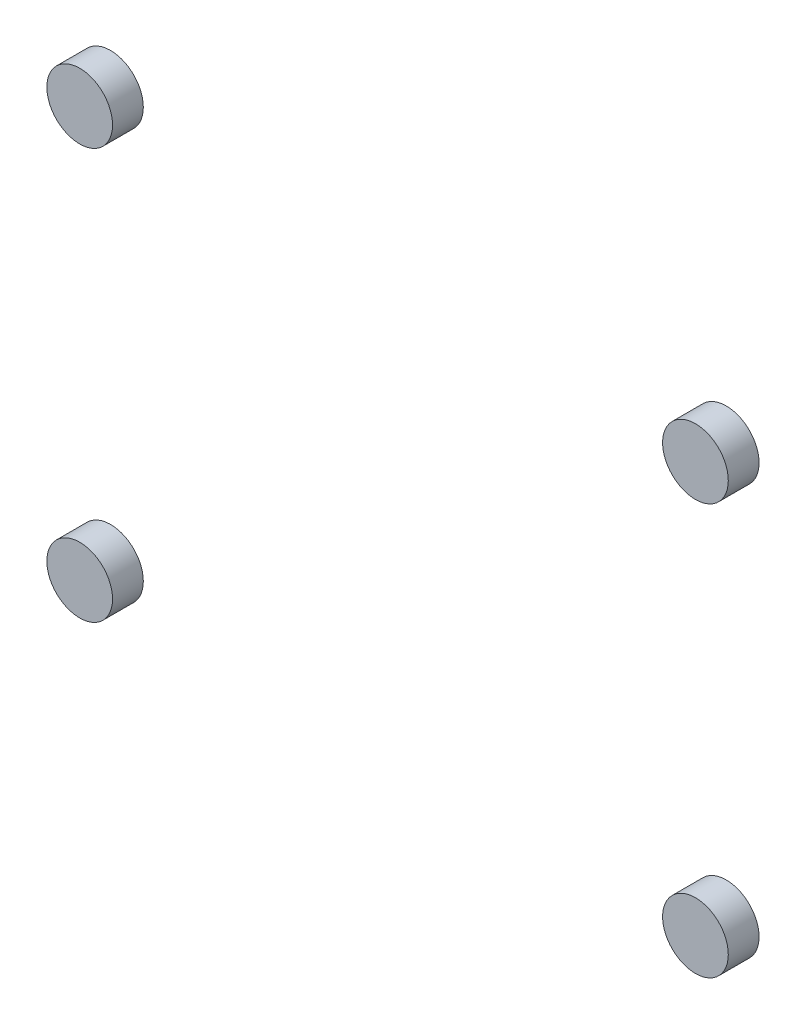
SolidWorks part; units mm, degrees
ref_plane "Front Plane" through (0, 0, 0) normal (0, 0, 1) x (1, 0, 0)
ref_plane "Top Plane" through (0, 0, 0) normal (0, 1, 0) x (1, 0, 0)
ref_plane "Right Plane" through (0, 0, 0) normal (1, 0, 0) x (0, 0, -1)
sketch "Sketch1" plane through (0, 0, 0) normal (0, 1, 0) x (1, 0, 0)
  line L0 (-35, -33) -> (35, -33)
  line L1 (43, -25) -> (43, 25)
  line L2 (35, 33) -> (-35, 33)
  line L3 (-43, 25) -> (-43, -25)
  arc A0 (43, -25) -> (35, -33) centre (35, -25) ccw
  arc A1 (35, 33) -> (43, 25) centre (35, 25) ccw
  arc A2 (-43, 25) -> (-35, 33) centre (-35, 25) ccw
  arc A3 (-35, -33) -> (-43, -25) centre (-35, -25) ccw
sketch "Sketch2" plane through (0, 0, 0) normal (0, 0, 1) x (1, 0, 0)
  line L1 (-17, -11) -> (17, -11)
  line L2 (-17, -11) -> (-17, 11)
  line L3 (-17, 11) -> (17, 11)
  line L4 (17, -11) -> (17, 11)
  line L5 (-17, -11) -> (17, 11) construction
  line L6 (-17, 11) -> (17, -11) construction
  circle A0 centre (-30, 0) radius 5.8824
  circle A1 centre (30, 0) radius 4.5
  circle A2 centre (0, -41.75) radius 4.5
  circle A3 centre (0, 41.75) radius 2.8971
sketch "Sketch3" plane through (0, 0, 0) normal (0, 0, 1) x (1, 0, 0)
  circle A0 centre (-30, -20) radius 3.2
  circle A1 centre (30, -20) radius 3.2
  circle A2 centre (-30, 20) radius 3.2
  circle A3 centre (30, 20) radius 3.2
extrude "Boss-Extrude2" add sketch "Sketch3" along normal blind 3
